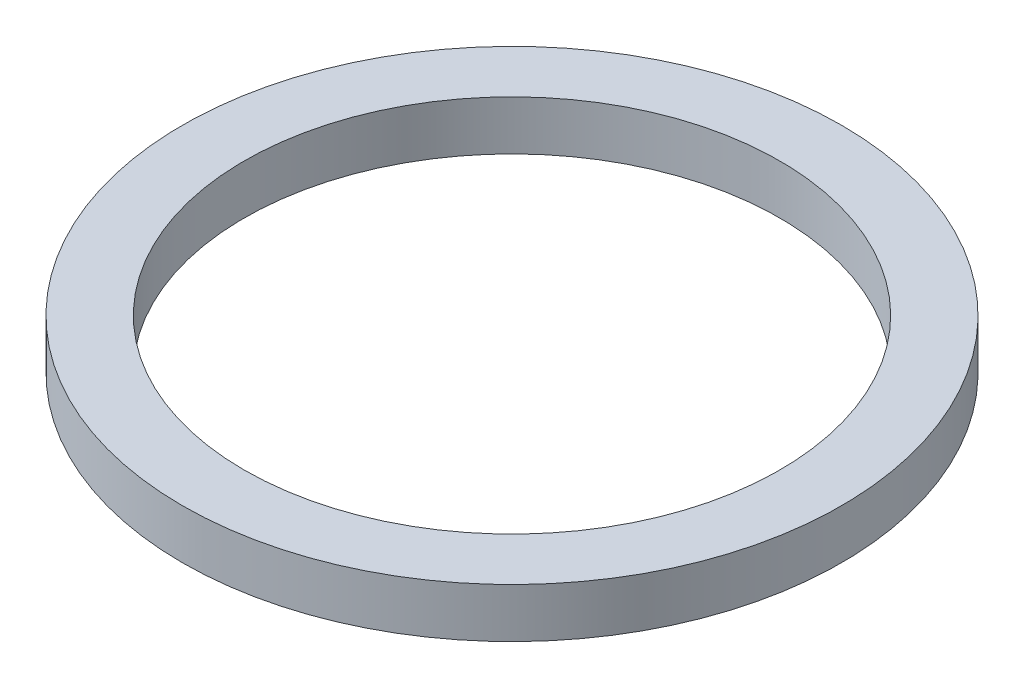
SolidWorks part; units mm, degrees
ref_plane "Front Plane" through (0, 0, 0) normal (0, 0, 1) x (1, 0, 0)
ref_plane "Top Plane" through (0, 0, 0) normal (0, 1, 0) x (1, 0, 0)
ref_plane "Right Plane" through (0, 0, 0) normal (1, 0, 0) x (0, 0, -1)
sketch "Sketch1" plane through (0, 0, 0) normal (0, 1, 0) x (1, 0, 0)
  circle A0 centre (0, 0) radius 40
  dimension "FLANGE_OD" = 80
extrude "Boss-Extrude1" add sketch "Sketch1" along normal blind 6
sketch "Sketch2" plane through (0, 0, 0) normal (0, 1, 0) x (1, 0, 0)
  circle A0 centre (0, 0) radius 32.5
  dimension "BORE_D" = 65
extrude "Cut-Extrude1" cut sketch "Sketch2" along normal through all
sketch "Sketch3" plane through (0, 6, 0) normal (0, 1, 0) x (1, 0, 0)
  circle A0 centre (0, 0) radius 18.2823 construction
  circle A1 centre (-18.2823, 0) radius 1.5
  dimension "BOLT_D" = 3
  dimension "BOLT_PCD" = 36.5646
extrude "Cut-Extrude2" cut sketch "Sketch3" against normal blind 3.9875 rebuild error yes
pattern_circular "CirPattern1" count 6 over 360 rebuild error yes
